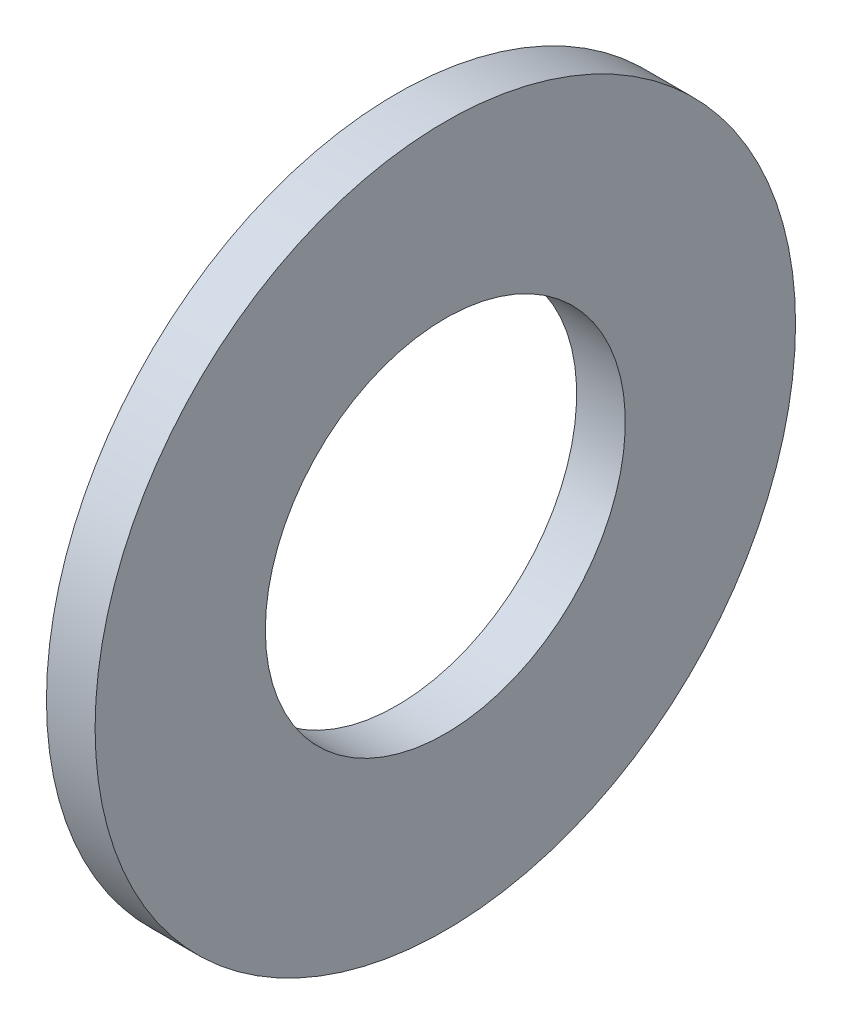
SolidWorks part; units mm, degrees
ref_plane "Plane1" through (0, 0, 0) normal (0, 0, 1) x (1, 0, 0)
ref_plane "Plane2" through (0, 0, 0) normal (0, 1, 0) x (1, 0, 0)
ref_plane "Plane3" through (0, 0, 0) normal (1, 0, 0) x (0, 0, -1)
sketch "Sketch1" plane through (0, 0, 0) normal (0, 0, 1) x (1, 0, 0)
  line L0 (-34.925, 0) -> (9.525, 0) construction
  line L1 (0, 18.5) -> (0, 36)
  line L2 (0, 36) -> (-5, 36)
  line L3 (-5, 36) -> (-5, 18.5)
  line L4 (-5, 18.5) -> (0, 18.5)
  dimension "Thickness" = 5
  dimension "Inside_dia" = 37
  dimension "Outside_dia" = 72
revolve "Base-Revolve" add sketch "Sketch1" angle 360 about L0
